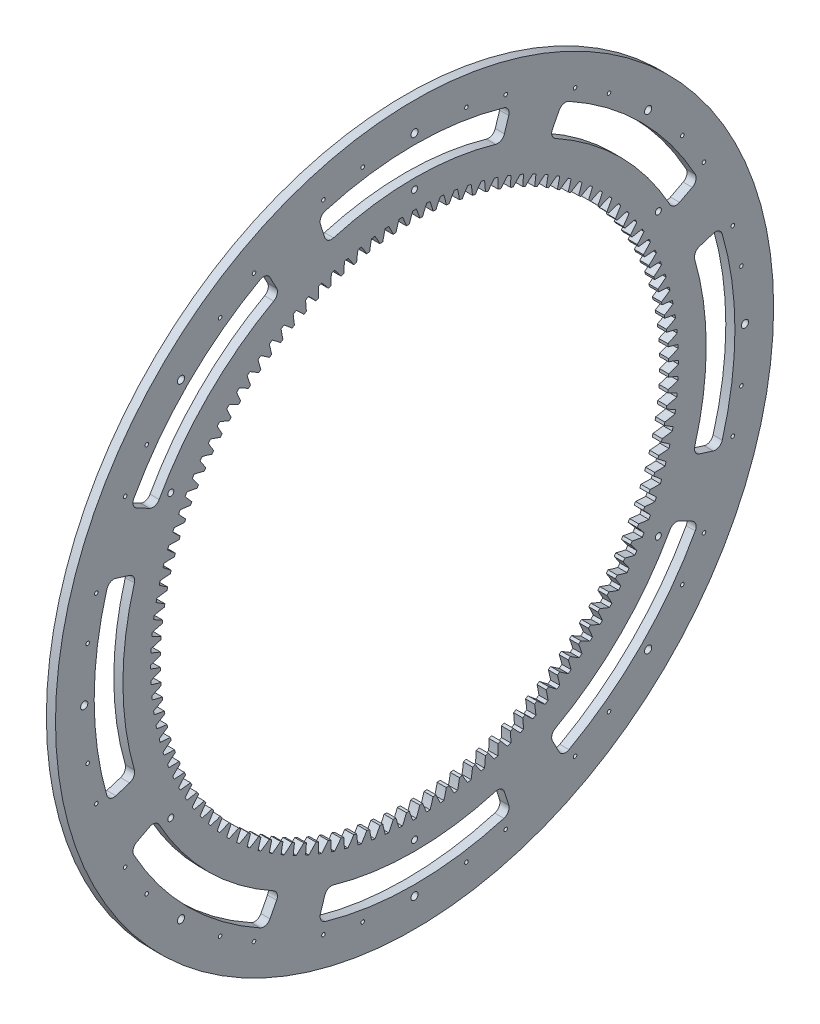
SolidWorks part; units mm, degrees
material "6061 Alloy"
ref_plane "Plane1" through (0, 0, 0) normal (0, 0, 1) x (1, 0, 0)
ref_plane "Plane2" through (0, 0, 0) normal (0, 1, 0) x (1, 0, 0)
ref_plane "Plane3" through (0, 0, 0) normal (1, 0, 0) x (0, 0, -1)
sketch "HoldingSke" plane through (0, 0, 0) normal (0, 1, 0) x (1, 0, 0)
  line L0 (0, 0) -> (-0.1667, -0.2887)
  line L1 (-15, 0) -> (100, 0) construction
  line L2 (0, 0) -> (-2.1039, 2.3779)
  line L3 (0, 0) -> (-11.863, 4.5341)
  line L4 (0, 0) -> (-4.318, 7.479)
  line L5 (0, 0) -> (-23.7986, -8.8762)
  line L6 (0, 0) -> (-10.5278, -7.1032)
  line L7 (-2.1039, 2.3779) -> (3.3635, 27.1825)
  line L8 (-76.2, 5.3779) -> (-54.61, 5.3779)
  line L9 (-71.009, 38.7566) -> (-53.1078, 45.2721)
  line L10 (-76.2, 71.12) -> (104.1128, 71.12)
  line L11 (0, 0) -> (-12.7, 0)
  line L12 (-76.2, 101.6) -> (-76.093, 101.6)
  line L13 (24.9733, 27.94) -> (52.9518, 28.4284)
  line L14 (24.9733, 27.94) -> (24.9743, 27.94)
  line L15 (24.9733, 27.94) -> (100.4006, 29.5858)
  circle A0 centre (0, 0) radius 250
  circle A1 centre (0, 0) radius 12.7
  circle A2 centre (0, 0) radius 12.7
  dimension "Num_teeth" = 120
  dimension "Pitch_radius" = 180.3128
  dimension "Width" = 12.7
  dimension "Thickness" = 12.7
  dimension "Diameter" = 500
sketch "BasProSke" plane through (0, 0, 0) normal (0, 1, 0) x (1, 0, 0)
  line L0 (-10, 0) -> (60, 0) construction
  line L1 (0, 177) -> (0, 250)
  line L2 (0, 177) -> (12.7, 177)
  line L3 (12.7, 177) -> (12.7, 250)
  line L4 (12.7, 250) -> (0, 250)
  dimension "Thickness" = 12.7
  dimension "Diameter" = 500
revolve "Base-Revolve" add sketch "BasProSke" angle 360 about L0
sketch "TooCutSke" plane through (0, 0, 0) normal (1, 0, 0) x (0, 0, -1)
  line L3 (2.6236, 179.9809) -> (2.6236, 53.6633) construction
  line L4 (0, 0) -> (0, 59.563) construction
  line L5 (0, 0) -> (-1.7886, 68.3041) construction
  line L6 (-82.281, 150.1278) -> (33.8449, 153.1686) construction
  circle A0 centre (0, 0) radius 180 construction
  circle A1 centre (0, 0) radius 183.751 construction
  circle A2 centre (0, 0) radius 152.2302 construction
  circle A3 centre (0, 0) radius 176.9746 construction
  arc A4 (3.6332, 176.9373) -> (1.204, 183.7471) centre (-82.281, 150.1278) ccw
  arc A5 (3.6332, 176.9373) -> (-3.6332, 176.9373) centre (0, 0) ccw
  arc A6 (1.204, 183.7471) -> (-1.204, 183.7471) centre (0, 0) ccw
  arc A7 (-1.204, 183.7471) -> (-3.6332, 176.9373) centre (82.281, 150.1278) ccw
extrude "ToothCut" cut sketch "TooCutSke" along normal through all
fillet "Breaks" [suppressed] radius 0.3
fillet "RootFillets" [suppressed] radius 0.751
pattern_circular "TeethCuts" count 120 over 360 about axis through (-10, 0, 0) along (1, 0, 0) of "RootFillets", "Breaks", "ToothCut"
sketch "Sketch1" plane through (12.7, 193.9697, 102.6282) normal (1, 0, 0) x (0, 0, -1)
  line L0 (102.6282, 36.0303) -> (102.6282, 2.0303)
  line L1 (102.6282, -193.9697) -> (33.4658, 25.3852) construction
  line L2 (102.6282, -193.9697) -> (171.7905, 25.3852) construction
  line L3 (37.0739, 13.9419) -> (40.0818, 4.4021)
  line L4 (168.1824, 13.9419) -> (165.1746, 4.4021)
  line L5 (39.1789, 27.5482) -> (66.5152, 33.6085) construction
  line L6 (52.8471, 30.5784) -> (102.6282, -193.9697) construction
  circle A0 centre (102.6282, -193.9697) radius 230
  circle A1 centre (102.6282, -193.9697) radius 196
  circle A2 centre (102.6282, 2.0303) radius 2
  circle A3 centre (102.6282, 36.0303) radius 3
  circle A4 centre (272.3691, -95.9697) radius 2
  circle A5 centre (272.3691, -291.9697) radius 2
  circle A6 centre (102.6282, -389.9697) radius 2
  circle A7 centre (-67.1128, -291.9697) radius 2
  circle A8 centre (-67.1128, -95.9697) radius 2
  circle A9 centre (265.2627, -31.3352) radius 3
  circle A10 centre (332.6282, -193.9697) radius 3
  circle A11 centre (265.2627, -356.6043) radius 3
  circle A12 centre (102.6282, -423.9697) radius 3
  circle A13 centre (-60.0064, -356.6043) radius 3
  circle A14 centre (-127.3718, -193.9697) radius 3
  circle A15 centre (-60.0064, -31.3352) radius 3
  circle A16 centre (102.6282, -193.9697) radius 250
  arc A17 (33.4658, 25.3852) -> (171.7905, 25.3852) centre (102.6282, -193.9697) cw
  arc A18 (40.4487, 20.2472) -> (164.8077, 20.2472) centre (102.6282, -193.9697) cw
  arc A19 (46.2389, 1.1023) -> (159.0175, 1.1023) centre (102.6282, -193.9697) cw
  arc A20 (38.5778, 9.172) -> (166.6785, 9.172) centre (102.6282, -193.9697) cw construction
  arc A21 (168.1824, 13.9419) -> (164.8077, 20.2472) centre (163.4139, 15.4454) ccw
  arc A22 (159.0175, 1.1023) -> (165.1746, 4.4021) centre (160.406, 5.9056) ccw
  arc A23 (46.2389, 1.1023) -> (40.0818, 4.4021) centre (44.8504, 5.9056) cw
  arc A24 (37.0739, 13.9419) -> (40.4487, 20.2472) centre (41.8425, 15.4454) cw
  circle A26 centre (39.1789, 27.5482) radius 1.5 construction
  circle A27 centre (66.5152, 33.6085) radius 1.5 construction
  circle A28 centre (138.7411, 33.6085) radius 1.5 construction
  circle A29 centre (166.0774, 27.5482) radius 1.5 construction
  point P21 (102.6282, -193.9697)
  point P35 (102.6282, -193.9697)
  point P36 (102.6282, 36.0303)
  point P46 (102.6282, 19.0303)
  point P47 (102.6282, 19.0303)
  point P50 (169.7032, 18.7652)
  point P53 (163.6891, -0.3092)
  point P56 (41.5672, -0.3092)
  point P59 (35.5531, 18.7652)
  point P65 (52.8471, 30.5784)
  dimension "D1" = 460
  dimension "D2" = 392
  dimension "D3" = 4
  dimension "D4" = 6
  dimension "D7" = 500
  dimension "D8" = 35
  dimension "D10" = 5
  dimension "D11" = 28
  dimension "D12" = 3
  dimension "D9" = 20
  dimension "D13" = 12.5
  dimension "D5" = 6
  dimension "D6" = 8
extrude "Cut-Extrude1" cut sketch "Sketch1" against normal up to next contours A19 A22 L4 A21 A18 A24 L3 A23
hole_wizard "Tap Drill for M6x1.0 Tap1" positions "3DSketch2" profile "Sketch3" hole size "M6x1.0" standard "ANSI Metric" end condition through all
sketch3d "3DSketch2"
  point P0 (12.7, 230, 0)
  point P6 (12.7, 162.6346, 162.6346)
  point P9 (12.7, 162.6346, -162.6346)
  point P11 (12.7, 0, 230)
  point P13 (12.7, 0, -230)
  point P15 (12.7, -162.6346, 162.6346)
  point P17 (12.7, -230, 0)
  point P19 (12.7, -162.6346, -162.6346)
sketch "Sketch3" plane through (12.7, 230, 0) normal (0, 1, 0) x (0, 0, -1)
  line L0 (0, 0) -> (0, 12.7)
  line L1 (0, 12.7) -> (2.5, 12.7)
  line L2 (2.5, 12.7) -> (2.5, 0)
  line L5 (2.5, 0) -> (0, 0)
  line L11 (0, -6.35) -> (0, 107.95) construction
  dimension "Thru Hole Dia." = 5
  dimension "Thru Hole Depth" = 12.7
hole_wizard "Tap Drill for M5x0.8 Tap1" positions "3DSketch4" profile "Sketch5" hole size "M5x0.8" standard "ANSI Metric" end condition through all
sketch3d "3DSketch4"
  point P0 (12.7, 196, 0)
  point P5 (12.7, 98, 169.741)
  point P7 (12.7, -98, 169.741)
  point P9 (12.7, -196, 0)
  point P11 (12.7, -98, -169.741)
  point P13 (12.7, 98, -169.741)
sketch "Sketch5" plane through (12.7, 196, 0) normal (0, 1, 0) x (0, 0, -1)
  line L0 (0, 0) -> (0, 12.7)
  line L1 (0, 12.7) -> (2.1, 12.7)
  line L2 (2.1, 12.7) -> (2.1, 0)
  line L5 (2.1, 0) -> (0, 0)
  line L11 (0, -6.35) -> (0, 107.95) construction
  dimension "Thru Hole Dia." = 4.2
  dimension "Thru Hole Depth" = 12.7
hole_wizard "Tap Drill for M3x0.5 Tap1" positions "3DSketch5" profile "Sketch6" hole size "M3x0.5" standard "ANSI Metric" end condition through all
sketch3d "3DSketch5"
  point P0 (12.7, 221.5179, 63.4493)
  point P2 (12.7, 227.5782, 36.113)
  point P9 (12.7, 227.5782, -36.113)
  point P11 (12.7, 221.5179, -63.4493)
sketch "Sketch6" plane through (12.7, 221.5179, 63.4493) normal (0, 1, 0) x (0, 0, -1)
  line L0 (0, 0) -> (0, 12.7)
  line L1 (0, 12.7) -> (1.25, 12.7)
  line L2 (1.25, 12.7) -> (1.25, 0)
  line L5 (1.25, 0) -> (0, 0)
  line L11 (0, -6.35) -> (0, 107.95) construction
  dimension "Thru Hole Dia." = 2.5
  dimension "Thru Hole Depth" = 12.7
pattern_circular "CirPattern1" count 8 over 360 about axis through (-10, 0, 0) along (-1, 0, 0) of "Cut-Extrude1", "Tap Drill for M3x0.5 Tap1"
sketch "Sketch7" plane through (12.7, 0, 0) normal (1, 0, 0) x (0, 0, -1)
  circle A1 centre (0, 0) radius 250
  circle A2 centre (0, 0) radius 250
  dimension "D1" = 0
extrude "Cut-Extrude2" cut sketch "Sketch7" against normal blind 6.35
equation "\"Pitch@HoldingSke\" = 1 / \"Module@HoldingSke\" "
equation "\"Overcut_dia@TooCutSke\" = (\"Num_teeth@HoldingSke\" - 2 * \"Addendum_fac@HoldingSke\") / \"Pitch@HoldingSke\" - 0.002 * 25.4"
equation "\"Pitch_dia@TooCutSke\" = \"Num_teeth@HoldingSke\" / \"Pitch@HoldingSke\""
equation "\"Base_dia@TooCutSke\" = \"Num_teeth@HoldingSke\" / \"Pitch@HoldingSke\" * cos((\"Ap@HoldingSke\"  * 3.14159265 / 180)) * 0.90"
equation "\"Root_dia@TooCutSke\" = \"Num_teeth@HoldingSke\"  / \"Pitch@HoldingSke\" + 2 *  \"Dedendum_fac@HoldingSke\"/ \"Pitch@HoldingSke\" + \"Dedendum_add@HoldingSke\" * 2"
equation "\"Half_ang@TooCutSke\" = 180 / \"Num_teeth@HoldingSke\""
equation "\"Half_CT@TooCutSke\" = \"Num_teeth@HoldingSke\" / \"Pitch@HoldingSke\" * sin((3.14159265 / 2 / \"Num_teeth@HoldingSke\")) / 2 + 10 * \"Backlash@HoldingSke\" / 4"
equation "\"Flank_rad@TooCutSke\" = \"Num_teeth@HoldingSke\" / \"Pitch@HoldingSke\" / 4"
equation "\"Radius@RootFillets\"= \"Clearance_fac@HoldingSke\" / \"Pitch@HoldingSke\" + \"Dedendum_add@HoldingSke\""
equation "\"Break_rad@Breaks\" = 0.02 / \"Pitch@HoldingSke\" * 5"
equation "\"Num_teeth@TeethCuts\" = int( \"Show_teeth@HoldingSke\" ) + 1"
equation "\"Num_teeth@TeethCuts\" = ((sgn( \"Num_teeth@TeethCuts\" - \"Num_teeth@HoldingSke\" )-1)*( \"Num_teeth@TeethCuts\" - \"Num_teeth@HoldingSke\" ))/-2+ \"Num_teeth@HoldingSke\""
equation "\"Num_teeth@TeethCuts\" = ((sgn( \"Num_teeth@TeethCuts\" - 2.0)+1)*( \"Num_teeth@TeethCuts\" - 2.0))/2 +2.0"
equation "\"Angle@TeethCuts\" = 360.0 / \"Num_teeth@HoldingSke\""
equation "\"Diameter@BasProSke\" = \"Num_teeth@HoldingSke\"  / \"Pitch@HoldingSke\" + 2 *  \"Dedendum_fac@HoldingSke\"/ \"Pitch@HoldingSke\" + \"Dedendum_add@HoldingSke\" * 2 + 0.002 * 25.4"
equation "\"Diameter@BasProSke\" = ((sgn( \"Diameter@BasProSke\"  - \"Diameter@HoldingSke\" )+1)*( \"Diameter@BasProSke\"  - \"Diameter@HoldingSke\" ))/2 + \"Diameter@HoldingSke\""
equation "\"Inside_diameter@BasProSke\" =  (\"Num_teeth@HoldingSke\" - 2 * \"Addendum_fac@HoldingSke\") / \"Pitch@HoldingSke\" "
equation "\"Thickness@BasProSke\"  = \"Width@HoldingSke\""
